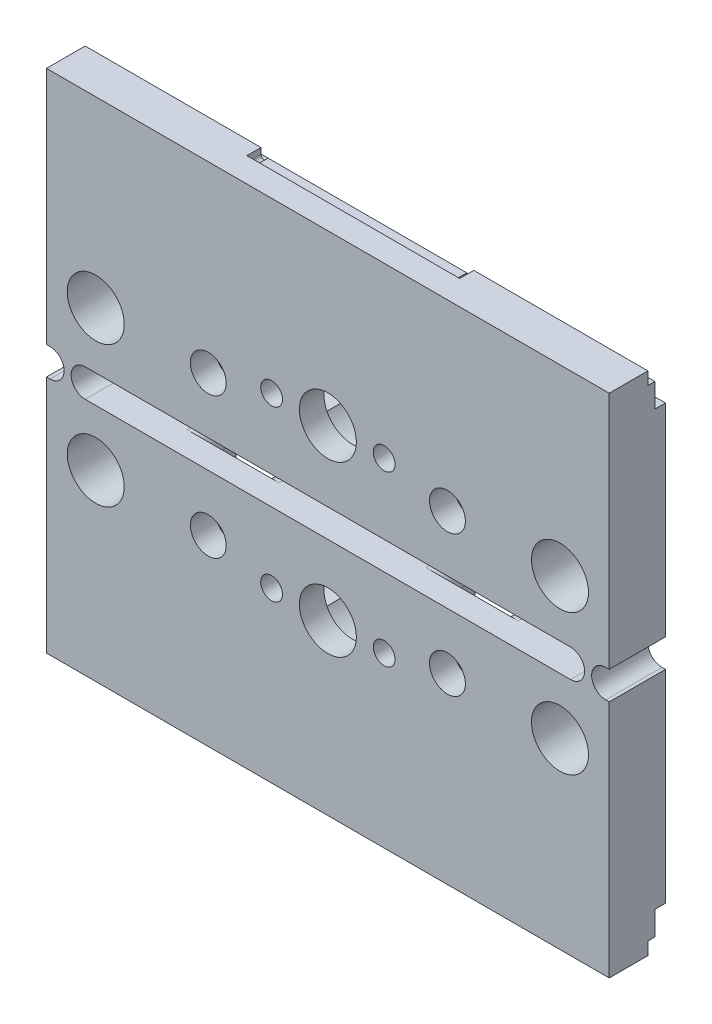
SolidWorks part; units mm, degrees
ref_plane "前视基准面" through (0, 0, 0) normal (0, 0, 1) x (1, 0, 0)
ref_plane "上视基准面" through (0, 0, 0) normal (0, 1, 0) x (1, 0, 0)
ref_plane "右视基准面" through (0, 0, 0) normal (1, 0, 0) x (0, 0, -1)
sketch "前视图草图" plane through (0, 0, 0) normal (0, 0, 1) x (1, 0, 0)
  line L0 (0, 0) -> (8.5179, 0) construction
  line L1 (0, 0) -> (0, 5.4227) construction
sketch "草图2" plane through (0, 0, 0) normal (0, 0, 1) x (1, 0, 0)
  line L0 (0, 0) -> (80, 0)
  line L1 (-200000, 0) -> (200008.5179, 0) construction
  line L2 (80, 0) -> (80, 34)
  line L3 (80, 34) -> (0, 34)
  line L4 (0, -200000) -> (0, 200005.4227) construction
  line L5 (0, 34) -> (0, 0)
  circle A0 centre (7, 8) radius 4.05
  circle A1 centre (40, 10) radius 4.05
  circle A2 centre (73, 8) radius 4.05
  dimension "D3" = 8
  dimension "D5" = 10
  dimension "D9" = 8.1
  dimension "D10" = 8.1
  dimension "D11" = 8.1
  dimension "D1" = 34
  dimension "D2" = 80
  dimension "D4" = 7
  dimension "D6" = 7
  dimension "D7" = 8
  dimension "D8" = 40
extrude "凸台-拉伸1" add sketch "草图2" along normal blind 8
sketch "草图3" plane through (0, 0, 8) normal (0, 0, 1) x (1, 0, 0)
  line L0 (16.088, 8) -> (31.4805, 8) construction
  line L1 (7, 8) -> (7, 16.8386) construction
  line L2 (73, 8) -> (73, 16.5917) construction
  line L4 (-200000, 0) -> (200008.5179, 0) construction
  circle A2 centre (23, 8) radius 2.55
  circle A3 centre (57, 8) radius 2.55
  dimension "D4" = 5.1
  dimension "D5" = 5.1
  dimension "D1" = 8
  dimension "D2" = 16
  dimension "D3" = 16
extrude "切除-拉伸1" cut sketch "草图3" against normal through all
sketch "草图4" plane through (80, 0, 0) normal (1, 0, 0) x (0, 0, -1)
  line L1 (0, -200000) -> (0, 200005.4227) construction
  line L2 (-1.5, 32.2) -> (-2.5, 32.2)
  line L3 (-2.5, 32.2) -> (-2.5, 34)
  line L4 (-8, 34) -> (0, 34) construction
  line L5 (-2.5, 34) -> (0, 34)
  line L6 (-1.5, 32.2) -> (-1.5, 28.8)
  line L7 (-1.5, 28.8) -> (0, 28.8)
  line L8 (0, 28.8) -> (0, 34)
  dimension "D1" = 3.4
  dimension "D2" = 2.5
  dimension "D3" = 1.5
  dimension "D4" = 1.8
extrude "切除-拉伸2" cut sketch "草图4" against normal through all
sketch "草图5" plane through (0, 0, 8) normal (0, 0, 1) x (1, 0, 0)
  line L0 (40, 10) -> (56.5376, 10) construction
  circle A0 centre (40, 10) radius 8 construction
  circle A1 centre (48, 10) radius 1.55
  circle A2 centre (32, 10) radius 1.55
  dimension "D1" = 3.1
  dimension "D2" = 3.1
  dimension "D3" = 16
extrude "切除-拉伸3" cut sketch "草图5" against normal through all
sketch "草图7" plane through (0, 0, 0) normal (0, 0, -1) x (-1, 0, 0)
  line L0 (-40, 12) -> (-40, -8.3696) construction
  line L1 (-23, 10) -> (-23, -2.3368) construction
  line L2 (200000, 0) -> (-200008.5179, 0) construction
  line L6 (-27.05, 10) -> (-27.05, 2.5)
  line L7 (-29.55, 0) -> (-16.45, 0)
  line L8 (-18.95, 2.5) -> (-18.95, 10)
  line L9 (-23, 8) -> (-23, 15.9045) construction
  line L13 (0, -200000) -> (0, 200005.4227) construction
  line L14 (-57, 8) -> (-57, 15.9045) construction
  line L15 (-57, 10) -> (-57, -2.3368) construction
  line L16 (-61.05, 2.5) -> (-61.05, 10)
  line L17 (-50.45, 0) -> (-63.55, 0)
  line L18 (-52.95, 10) -> (-52.95, 2.5)
  arc A1 (-18.95, 10) -> (-27.05, 10) centre (-23, 10) ccw
  arc A4 (-29.55, 0) -> (-27.05, 2.5) centre (-29.55, 2.5) ccw
  arc A5 (-18.95, 2.5) -> (-16.45, 0) centre (-16.45, 2.5) ccw
  arc A7 (-61.05, 2.5) -> (-63.55, 0) centre (-63.55, 2.5) cw
  arc A8 (-50.45, 0) -> (-52.95, 2.5) centre (-50.45, 2.5) cw
  arc A9 (-61.05, 10) -> (-52.95, 10) centre (-57, 10) cw
  dimension "D1" = 40
  dimension "D4" = 8.1
  dimension "D7" = 2.5
  dimension "D8" = 2.5
  dimension "D3" = 10
extrude "切除-拉伸4" cut sketch "草图7" against normal blind 4.5
sketch "草图8" plane through (0, 0, 0) normal (0, 0, -1) x (-1, 0, 0)
  line L0 (-40, 10) -> (-57.3165, 10) construction
  line L1 (-40, 20) -> (-40, 35.6562) construction
  line L2 (-30.5, 12.85) -> (-49.5, 12.85)
  line L3 (-49.5, 7.15) -> (-30.5, 7.15)
  line L4 (200000, 0) -> (-200008.5179, 0) construction
  arc A0 (-30.5, 7.15) -> (-30.5, 12.85) centre (-30.5, 10) ccw
  arc A1 (-49.5, 12.85) -> (-49.5, 7.15) centre (-49.5, 10) ccw
  dimension "D1" = 5.7
  dimension "D2" = 9.5
  dimension "D3" = 9.5
  dimension "D4" = 10
extrude "切除-拉伸5" cut sketch "草图8" against normal blind 4.5
sketch "草图20" plane through (0, 0, 0) normal (0, 0, -1) x (-1, 0, 0)
  circle A0 centre (-40, 10) radius 5.5
  dimension "D1" = 11
extrude "切除-拉伸12" cut sketch "草图20" against normal blind 4.5
sketch "草图19" plane through (0, 0, 2.5) normal (0, 0, -1) x (-1, 0, 0)
  line L0 (0, 34) -> (-80, 34) construction
  line L1 (-25, 34) -> (-55.2479, 34)
  line L2 (-25, 34) -> (-25, 33.2)
  line L3 (-26, 33.2) -> (-54.2479, 33.2)
  line L4 (-55.2479, 34) -> (-55.2479, 33.2)
  line L5 (0, -200000) -> (0, 200005.4227) construction
  line L7 (0, 32.2) -> (-80, 32.2) construction
  line L8 (-56.3335, 32.7) -> (-52.9089, 32.7) construction
  line L9 (-55.2479, 1028.5823) -> (-55.2479, 33.2) construction
  line L10 (-25, 1028.5823) -> (-25, 32.7) construction
  line L11 (-55.2479, 32.7) -> (-55.2479, -973.3) construction
  line L12 (-25, 32.7) -> (-25, -973.3) construction
  arc A3 (-55.2479, 33.2) -> (-54.2479, 33.2) centre (-54.7479, 33.2) ccw
  arc A6 (-26, 33.2) -> (-25, 33.2) centre (-25.5, 33.2) ccw
  dimension "D3" = 1
  dimension "D4" = 1
  dimension "D2" = 0.8
  dimension "D1" = 0.5
  dimension "D9" = 25
extrude "切除-拉伸11" cut sketch "草图19" against normal blind 2
sketch "草图22" plane through (0, 0, 8) normal (0, 0, 1) x (1, 0, 0)
  line L1 (0, -200000) -> (0, 200005.4227) construction
  line L2 (0.5, -4) -> (5.5, -4)
  line L4 (79.5, 0) -> (74.5, 0)
  line L5 (3.5, 1.9875) -> (3.5, -4.1402) construction
  line L6 (76.5, -11.5647) -> (76.5, -5.1636) construction
  line L7 (80, 0) -> (80, 34) construction
  line L8 (74.5, -4) -> (79.5, -4)
  line L9 (5.5, 0) -> (0.5, 0)
  line L10 (77.5, -2.9635) -> (77.5, -4.3032) construction
  line L11 (2.5, -8.393) -> (2.5, -15.1693) construction
  arc A0 (5.5, 0) -> (5.5, -4) centre (5.5, -2) ccw
  arc A1 (74.5, -4) -> (74.5, 0) centre (74.5, -2) ccw
  arc A2 (0.5, -4) -> (0.5, 0) centre (0.5, -2) ccw
  arc A3 (79.5, 0) -> (79.5, -4) centre (79.5, -2) ccw
  dimension "D1" = 3.5
  dimension "D2" = 3.5
  dimension "D3" = 4
  dimension "D4" = 2.5
  dimension "D5" = 2.5
extrude "凸台-拉伸2" add sketch "草图22" against normal blind 8
ref_plane "基准面1" through (0, -2, 0) normal (0, -1, 0) x (-1, 0, 0)
mirror "镜向2" about plane through (0, -2, 0) normal (0, -1, 0) of "切除-拉伸3", "凸台-拉伸1", "切除-拉伸1", "切除-拉伸2", "切除-拉伸4", "切除-拉伸5", "切除-拉伸12", "切除-拉伸11"
sketch "草图23" plane through (0, 0, 0) normal (0, 0, -1) x (-1, 0, 0)
  line L0 (-80, 0) -> (0, 0)
  line L1 (0, 0) -> (0, -4)
  line L2 (0, -4) -> (-80, -4)
  line L3 (-80, -4) -> (-80, 0)
sketch "草图24" plane through (0, 0, 8) normal (0, 0, 1) x (1, 0, 0)
  line L0 (80, -4) -> (80, 0)
  line L1 (80, 0) -> (0, 0)
  line L2 (0, 0) -> (0, -4)
  line L3 (0, -4) -> (80, -4)
